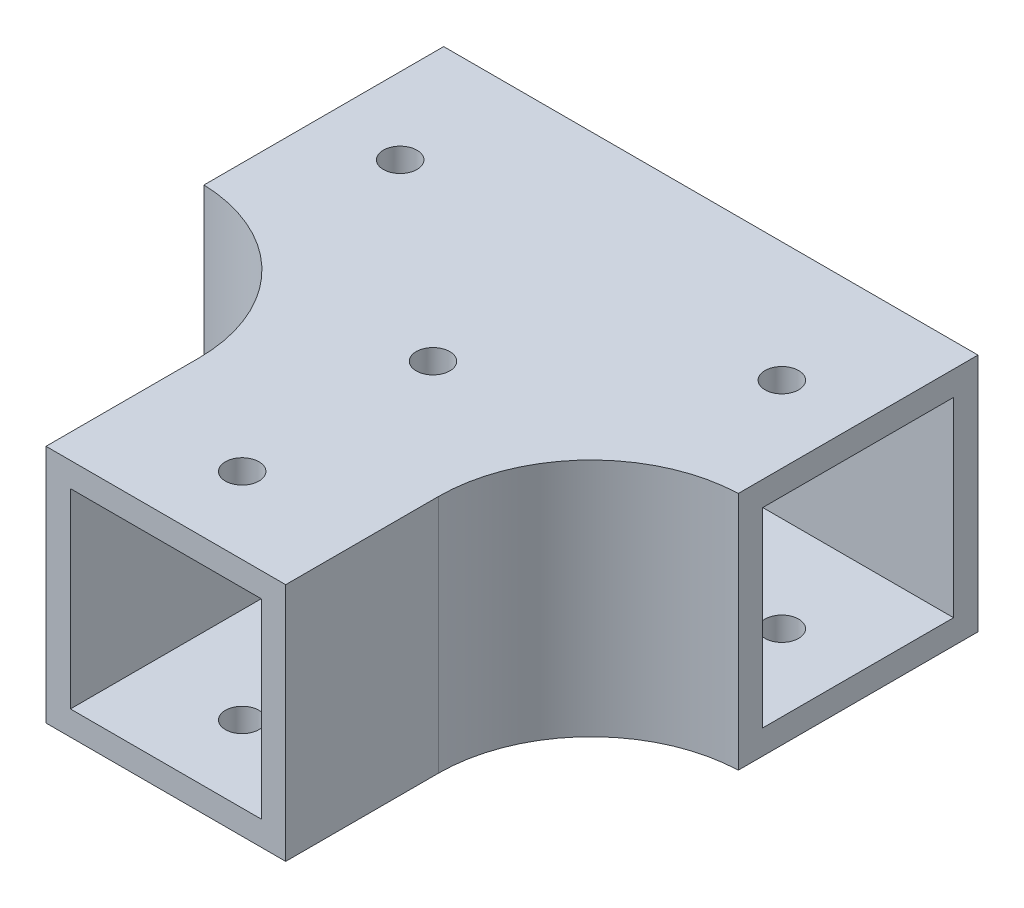
SolidWorks part; units mm, degrees
ref_plane "Front" through (0, 0, 0) normal (0, 0, 1) x (1, 0, 0)
ref_plane "Top" through (0, 0, 0) normal (0, 1, 0) x (1, 0, 0)
ref_plane "Right" through (0, 0, 0) normal (1, 0, 0) x (0, 0, -1)
sketch "Эскиз1" plane through (0, 0, 0) normal (1, 0, 0) x (0, 0, -1)
  line L1 (-12.5, -12.5) -> (12.5, -12.5)
  line L2 (-12.5, -12.5) -> (-12.5, 12.5)
  line L3 (-12.5, 12.5) -> (12.5, 12.5)
  line L4 (12.5, -12.5) -> (12.5, 12.5)
  line L5 (-12.5, -12.5) -> (12.5, 12.5) construction
  line L6 (-12.5, 12.5) -> (12.5, -12.5) construction
  point P0 (0, 0)
  dimension "D1" = 25
  dimension "D2" = 25
extrude "Вытянуть-Тонкостенный1" add sketch "Эскиз1" along normal blind 70 thin thin type one direction wall 3.2
sketch "Эскиз2" plane through (0, 0, 15.7) normal (0, 0, 1) x (1, 0, 0)
  line L0 (35, 15.7) -> (35, -15.7) construction
  line L1 (70, 15.7) -> (0, 15.7) construction
  line L2 (70, -15.7) -> (0, -15.7) construction
  line L4 (22.5, 12.5) -> (47.5, 12.5)
  line L5 (22.5, 12.5) -> (22.5, -12.5)
  line L6 (22.5, -12.5) -> (47.5, -12.5)
  line L7 (47.5, 12.5) -> (47.5, -12.5)
  line L8 (22.5, 12.5) -> (47.5, -12.5) construction
  line L9 (22.5, -12.5) -> (47.5, 12.5) construction
  point P6 (35, 0)
  dimension "D1" = 25
  dimension "D2" = 25
extrude "Вытянуть-Тонкостенный2" add sketch "Эскиз2" along normal blind 40 thin thin type one direction wall 3.2
sketch "Эскиз3" plane through (0, 0, 15.7) normal (0, 0, 1) x (1, 0, 0)
  line L1 (22.5, 12.5) -> (47.5, 12.5)
  line L2 (22.5, 12.5) -> (22.5, -12.5)
  line L3 (22.5, -12.5) -> (47.5, -12.5)
  line L4 (47.5, 12.5) -> (47.5, -12.5)
extrude "Вырез-Вытянуть1" cut sketch "Эскиз3" against normal up to next
fillet "Скругление1" radius 20 2 edges at (50.7, 0, 15.7) (19.3, 0, 15.7)
sketch "Эскиз4" plane through (0, 15.7, 0) normal (0, 1, 0) x (1, 0, 0)
  line L0 (0, 0) -> (70, 0) construction
  line L1 (70, 15.7) -> (70, -15.7) construction
  line L2 (35, -55.7) -> (35, 0) construction
  line L3 (50.7, -55.7) -> (19.3, -55.7) construction
  line L4 (0, 15.7) -> (0, -15.7) construction
  circle A0 centre (10, 0) radius 2.2
  circle A1 centre (60, 0) radius 2.2
  circle A2 centre (35, -45.7) radius 2.2
  circle A3 centre (35, -20.7) radius 2.2
  dimension "D1" = 10
  dimension "D2" = 10
  dimension "D3" = 10
  dimension "D4" = 35
extrude "Вырез-Вытянуть2" cut sketch "Эскиз4" against normal through all
